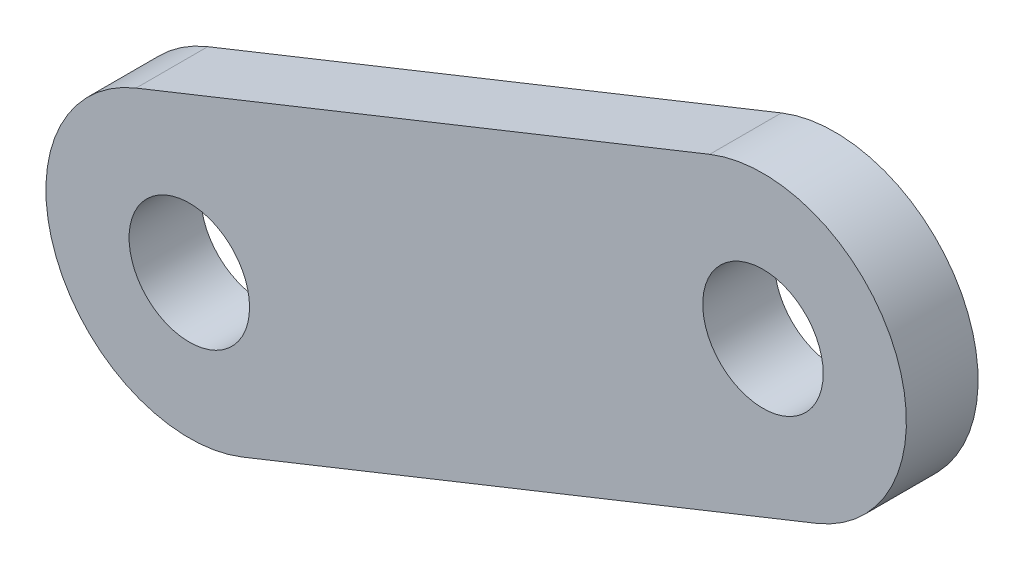
SolidWorks part; units mm, degrees
material "6061-T6 (SS)"
ref_plane "Alzado" through (0, 0, 0) normal (0, 0, 1) x (1, 0, 0)
ref_plane "Planta" through (0, 0, 0) normal (0, 1, 0) x (1, 0, 0)
ref_plane "Vista lateral" through (0, 0, 0) normal (1, 0, 0) x (0, 0, -1)
ref_plane "Plano1" through (0, 0, 51.9) normal (0, 0, 1) x (1, 0, 0)
sketch "Sk_Biela_interior" plane through (0, 0, 51.9) normal (0, 0, 1) x (1, 0, 0)
  line L0 (-42.143, -54.6424) -> (-22.143, -46.6424)
  line L1 (-25.857, -37.3576) -> (-45.857, -45.3576)
  arc A0 (-22.143, -46.6424) -> (-25.857, -37.3576) centre (-24, -42) ccw
  arc A1 (-45.857, -45.3576) -> (-42.143, -54.6424) centre (-44, -50) ccw
  circle A2 centre (-24, -42) radius 2.1
  circle A3 centre (-44, -50) radius 2.1
extrude "Biela_interior" add sketch "Sk_Biela_interior" along normal blind 2.5
